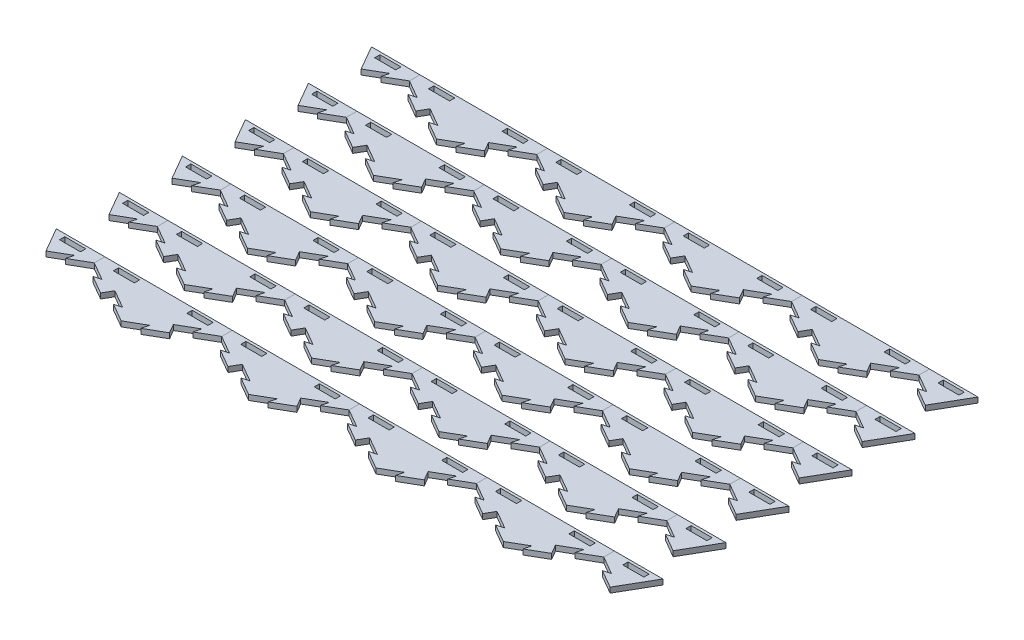
SolidWorks part; units mm, degrees
note: '?' marks a value the reader was unsure of.
material "Cedar"
ref_plane "Front Plane" through (0, 0, 0) normal (0, 0, 1) x (1, 0, 0)
ref_plane "Top Plane" through (0, 0, 0) normal (0, 1, 0) x (1, 0, 0)
ref_plane "Right Plane" through (0, 0, 0) normal (1, 0, 0) x (0, 0, -1)
sketch "Sketch1" plane through (0, 0, 0) normal (0, 1, 0) x (1, 0, 0)
  line L0 (-76.9897, 0) -> (76.9897, 0) construction
  line L1 (-76.9897, 0) -> (0, -44.45)
  line L2 (0, -44.45) -> (76.9897, 0)
  line L3 (76.9897, 0) -> (76.9897, 88.9)
  line L4 (76.9897, 88.9) -> (0, 133.35)
  line L5 (0, 133.35) -> (-76.9897, 88.9)
  line L6 (-76.9897, 88.9) -> (-76.9897, 0)
  line L7 (0, -44.45) -> (0, 44.45) construction
  circle A0 centre (0, 44.45) radius 76.9897 construction
  point P9 (0, 0)
  dimension "D1" = 88.9
extrude "Boss-Extrude1" add sketch "Sketch1" against normal blind 6.35
sketch "Sketch2" plane through (0, 0, 0) normal (0, 1, 0) x (1, 0, 0)
  line L0 (-76.9897, 44.45) -> (76.9897, 44.45) construction
  line L1 (-76.9897, 88.9) -> (-76.9897, 0) construction
  line L2 (76.9897, 0) -> (76.9897, 88.9) construction
  point P2 (0, 44.45)
ref_axis "Axis1" through (0, 0, -44.45) along (0, 1, 0)?
sketch "Sketch10" plane through (0, 0, 0) normal (0, 1, 0) x (1, 0, 0)
  line L0 (0, -44.45) -> (-21.997, -31.75) construction
  line L1 (-21.997, -31.75) -> (-13.3228, -29.4257)
  line L2 (-13.3228, -29.4257) -> (-35.3198, -16.7257)
  line L3 (-35.3198, -16.7257) -> (-38.4948, -22.225)
  line L4 (-21.997, -31.75) -> (-38.4948, -22.225)
  line L5 (-76.9897, 0) -> (0, -44.45) construction
  dimension "D1" = 45
  dimension "D2" = 6.35
extrude "Cut-Extrude4" cut sketch "Sketch10" against normal through all
sketch "Sketch11" plane through (0, 0, 0) normal (0, 1, 0) x (1, 0, 0)
  line L0 (-38.4948, -22.225) -> (-76.9897, 0) construction
  line L1 (-38.4948, -22.225) -> (-41.6698, -27.7243)
  line L2 (-41.6698, -27.7243) -> (-63.6669, -15.0243)
  line L3 (-63.6669, -15.0243) -> (-54.9926, -12.7)
  line L4 (-54.9926, -12.7) -> (-38.4948, -22.225)
  line L5 (-54.9926, -12.7) -> (-76.9897, 0) construction
  line L6 (-54.9926, -12.7) -> (-76.9897, 0) construction
  line L7 (-76.9897, 0) -> (-38.4948, -22.225) construction
  line L8 (-76.9897, 88.9) -> (-76.9897, 0) construction
  dimension "D1" = 45
  dimension "D2" = 6.35
extrude "Boss-Extrude4" add sketch "Sketch11" against normal blind 6.35 contours L1 L2 L3 L4
pattern_circular "CirPattern1" count 2 every 60 about axis through (0, 0, -44.45) along (0, 1, 0) of "Cut-Extrude4", "Boss-Extrude4"
sketch "Sketch12" plane through (0, 0, 0) normal (0, 1, 0) x (1, 0, 0)
  line L0 (-76.9897, 12.7) -> (76.9897, 12.7)
  line L1 (-76.9897, 88.9) -> (-76.9897, 0) construction
  line L2 (76.9897, 0) -> (76.9897, 88.9) construction
  line L3 (76.9897, 12.7) -> (76.9897, 133.35)
  line L4 (76.9897, 133.35) -> (-76.9897, 133.35)
  line L5 (-76.9897, 133.35) -> (-76.9897, 12.7)
  line L6 (0, 0) -> (0, 12.7) construction
  dimension "D1" = 12.7
extrude "Cut-Extrude5" cut sketch "Sketch12" against normal through all
sketch "Sketch13" plane through (0, 0, 0) normal (0, 1, 0) x (1, 0, 0)
  line L0 (0, 0) -> (0, 12.7) construction
  line L1 (-76.9897, 12.7) -> (76.9897, 12.7) construction
  line L2 (-44.45, 6.35) -> (44.45, 6.35) construction
  line L4 (-57.15, 9.525) -> (-31.75, 9.525)
  line L5 (-57.15, 9.525) -> (-57.15, 3.175)
  line L6 (-57.15, 3.175) -> (-31.75, 3.175)
  line L7 (-31.75, 9.525) -> (-31.75, 3.175)
  line L8 (-57.15, 9.525) -> (-31.75, 3.175) construction
  line L9 (-57.15, 3.175) -> (-31.75, 9.525) construction
  line L10 (31.75, 9.525) -> (57.15, 9.525)
  line L11 (31.75, 9.525) -> (31.75, 3.175)
  line L12 (31.75, 3.175) -> (57.15, 3.175)
  line L13 (57.15, 9.525) -> (57.15, 3.175)
  line L14 (31.75, 9.525) -> (57.15, 3.175) construction
  line L15 (31.75, 3.175) -> (57.15, 9.525) construction
  point P7 (0, 6.35)
  point P8 (0, 6.35)
  dimension "D1" = 6.35
  dimension "D2" = 25.4
  dimension "D3" = 6.35
  dimension "D4" = 25.4
  dimension "D5" = 88.9
extrude "Cut-Extrude6" cut sketch "Sketch13" against normal through all
pattern_linear "LPattern1" count 5 spacing 153.9793 along (1, 0, 0) count 2 spacing 153.9793 along (-1, 0, 0) pattern seed only yes of bodies 136 131
sketch "Sketch14" plane through (0, 0, 0) normal (0, 1, 0) x (1, 0, 0)
  line L0 (615.9173, -44.45) -> (615.9173, 12.7)
  line L1 (538.9276, 12.7) -> (692.9069, 12.7) construction
  line L2 (615.9173, 12.7) -> (692.9069, 12.7)
  line L3 (692.9069, 12.7) -> (692.9069, -44.45)
  line L4 (692.9069, -44.45) -> (615.9173, -44.45)
  line L5 (-153.9793, -44.45) -> (-153.9793, 12.7)
  line L6 (-230.969, 12.7) -> (-76.9897, 12.7) construction
  line L7 (-153.9793, 12.7) -> (-230.969, 12.7)
  line L8 (-230.969, 12.7) -> (-230.969, -44.45)
  line L9 (-230.969, -44.45) -> (-153.9793, -44.45)
  line L10 (580.5974, -16.7257) -> (597.5864, 12.7)
  line L11 (597.5864, 12.7) -> (615.9173, 12.7)
  line L12 (580.5974, -16.7257) -> (574.2474, -27.7243)
  line L13 (574.2474, -27.7243) -> (615.9173, -44.45)
  line L14 (-112.3095, -27.7243) -> (-135.6484, 12.7)
  line L15 (-135.6484, 12.7) -> (-153.9793, 12.7)
  line L16 (-112.3095, -27.7243) -> (-134.3065, -40.4243)
  line L17 (-134.3065, -40.4243) -> (-153.9793, -44.45)
  line L18 (-118.6595, -16.7257) -> (-112.3095, -27.7243) construction
  line M5 (673.0673, 9.525) -> (673.0673, 3.175)
  line M6 (673.0673, 3.175) -> (647.6673, 3.175)
  line M7 (647.6673, 3.175) -> (647.6673, 9.525)
  line M8 (647.6673, 9.525) -> (673.0673, 9.525)
  line M13 (692.9069, 12.7) -> (538.9276, 12.7)
  line M19 (580.5974, -16.7257) -> (602.5945, -29.4257)
  line M20 (602.5945, -29.4257) -> (593.9202, -31.75)
  line M21 (593.9202, -31.75) -> (615.9173, -44.45)
  line M22 (615.9173, -44.45) -> (637.9143, -31.75)
  line M23 (637.9143, -31.75) -> (635.5901, -40.4243)
  line M24 (635.5901, -40.4243) -> (657.5871, -27.7243)
  line M25 (657.5871, -27.7243) -> (651.2371, -16.7257)
  line M26 (651.2371, -16.7257) -> (673.2341, -4.0257)
  line M27 (673.2341, -4.0257) -> (670.9099, -12.7)
  line M28 (670.9099, -12.7) -> (692.9069, 0)
  line M29 (692.9069, 0) -> (692.9069, 12.7)
extrude "Cut-Extrude7" cut sketch "Sketch14" against normal through all contours L17 L16 L14 L15 L5 | L10 L0 M19 M20 M21 M13 | L0 M22 M23 M24 M25 M26 M27 M28 M29 M13 M8 M5 M6 M7 | L8 L9 L5 L7
pattern_linear "LPattern2" count 6 spacing 76.2 along (0, 0, 1) of bodies 144 134 133 132 136 145
